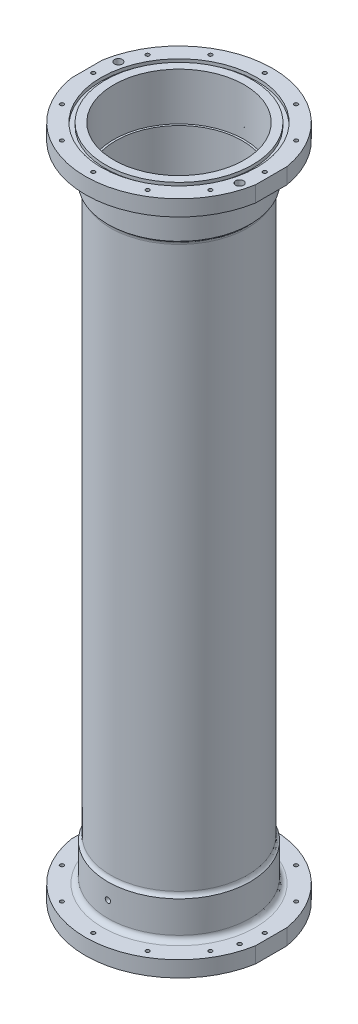
SolidWorks part; units mm, degrees
material "6061-T6 (SS)"
ref_plane "Front Plane" through (0, 0, 0) normal (0, 0, 1) x (1, 0, 0)
ref_plane "Top Plane" through (0, 0, 0) normal (0, 1, 0) x (1, 0, 0)
ref_plane "Right Plane" through (0, 0, 0) normal (1, 0, 0) x (0, 0, -1)
sketch "Sketch2" plane through (0, 0, 0) normal (0, 1, 0) x (1, 0, 0)
  circle A0 centre (0, 0) radius 38.1
  circle A1 centre (0, 0) radius 41.275
  dimension "D1" = 82.55
  dimension "D2" = 76.2
extrude "Base Cylinder" add sketch "Sketch2" along normal blind 406.4
sketch "Sketch3" plane through (0, 0, 0) normal (0, -1, 0) x (1, 0, 0)
  circle A0 centre (0, 0) radius 38.1
  circle A1 centre (0, 0) radius 56.3562
  dimension "D1" = 112.7125
extrude "Aft Flange" add sketch "Sketch3" against normal blind 9.525
sketch "Sketch34" plane through (0, 0, 0) normal (0, -1, 0) x (1, 0, 0)
  circle A0 centre (0, 0) radius 39.2906
  dimension "D1" = 78.5812
extrude "TemperatureInsert" cut sketch "Sketch34" against normal blind 28.575
sketch "Sketch6" plane through (0, 0, 0) normal (0, -1, 0) x (1, 0, 0)
  circle A0 centre (0, 0) radius 46.9011
  circle A1 centre (0, 0) radius 44.2849
  dimension "D1" = 93.8022
  dimension "D2" = 88.5698
extrude "Aft O-Ring" cut sketch "Sketch6" against normal blind 1.9812
sketch "Sketch33" plane through (0, 9.525, 0) normal (0, 1, 0) x (1, 0, 0)
  circle A0 centre (0, 0) radius 41.275
  circle A1 centre (0, 0) radius 42.8625
  dimension "D1" = 82.55
  dimension "D2" = 85.725
extrude "CriticalBoss" add sketch "Sketch33" along normal blind 22.225
sketch "Sketch For Bolt Holes" plane through (0, 0, 0) normal (0, -1, 0) x (1, 0, 0)
  circle A0 centre (-51.6255, 0) radius 1.5875
  circle A1 centre (-44.709, 25.8128) radius 1.5875
  circle A2 centre (-25.8128, 44.709) radius 1.5875
  circle A3 centre (0, 51.6255) radius 1.5875
  circle A4 centre (25.8127, 44.709) radius 1.5875
  circle A5 centre (44.709, 25.8128) radius 1.5875
  circle A6 centre (51.6255, 0) radius 1.5875
  circle A7 centre (44.709, -25.8127) radius 1.5875
  circle A8 centre (25.8128, -44.709) radius 1.5875
  circle A9 centre (0, -51.6255) radius 1.5875
  circle A10 centre (-25.8127, -44.709) radius 1.5875
  circle A11 centre (-44.709, -25.8128) radius 1.5875
  point P36 (0, 0)
  dimension "D2" = 3.175
  dimension "D1" = 51.6255
  dimension "D3" = 12
hole_wizard "Bolt Circle" positions "Sketch8" profile "Sketch9" hole size "#4-40" standard "ANSI Inch"
sketch "Sketch8" plane through (0, 0, 0) normal (0, -1, 0) x (-1, 0, 0)
  point P0 (-25.8127, -44.709)
  point P3 (-44.709, -25.8128)
  point P6 (-51.6255, 0)
  point P9 (-44.709, 25.8127)
  point P12 (-25.8128, 44.709)
  point P15 (0, 51.6255)
  point P18 (25.8127, 44.709)
  point P21 (44.709, 25.8128)
  point P24 (51.6255, 0)
  point P27 (44.709, -25.8128)
  point P30 (25.8128, -44.709)
  point P33 (0, -51.6255)
  point P36 (-25.8127, -44.709)
  point P38 (-44.709, -25.8128)
  point P40 (-51.6255, 0)
sketch "Sketch9" plane through (25.8127, 0, 44.709) normal (1, 0, 0) x (0, 0, -1)
  line L0 (0, 0) -> (0, 26.0792)
  line L1 (0, 26.0792) -> (1.1303, 25.4)
  line L2 (1.1303, 25.4) -> (1.1303, 0)
  line L5 (1.1303, 0) -> (0, 0)
  line L10 (0, 26.0792) -> (-1.1303, 25.4) construction
  line L11 (0, -6.35) -> (0, 107.95) construction
  dimension "Hole Dia." = 2.2606
  dimension "Hole Depth" = 25.4
  dimension "Drill Angle" = 118
fillet "CriticalBoss Flange" radius 3.175 2 edges at (0, 31.75, 41.275) (0, 9.525, -42.8625)
sketch "Dowel Hole Sketch" plane through (0, 0, 0) normal (0, -1, 0) x (1, 0, 0)
  line L0 (0, 0) -> (-51.6255, 0) construction
  line L1 (0, 0) -> (-49.8664, -13.3617) construction
  line L2 (0, 0) -> (0, -51.6255) construction
  line L3 (0, 0) -> (49.8664, 13.3617) construction
  circle A0 centre (0, 0) radius 51.6255
  circle A1 centre (-49.8664, -13.3617) radius 4.6172
  circle A2 centre (49.8664, 13.3617) radius 3.4532
  dimension "D1" = 15
hole_wizard "3/16 (0.1875) Press Dowel Hole1" positions "Sketch14" profile "Sketch12" hole size "3/16" standard "ANSI Inch"
sketch "Sketch14" plane through (0, 0, 0) normal (0, -1, 0) x (-1, 0, 0)
  point P0 (49.8664, 13.3617)
  point P3 (-49.8664, -13.3617)
sketch "Sketch12" plane through (-49.8664, 0, -13.3617) normal (1, 0, 0) x (0, 0, -1)
  line L0 (0, 0) -> (0, 7.7808)
  line L1 (0, 7.7808) -> (2.3812, 6.35)
  line L2 (2.3812, 6.35) -> (2.3812, 0)
  line L5 (2.3812, 0) -> (0, 0)
  line L10 (0, 7.7808) -> (-2.3813, 6.35) construction
  line L11 (0, -6.35) -> (0, 107.95) construction
  dimension "Hole Dia." = 4.7625
  dimension "Hole Depth" = 6.35
  dimension "Drill Angle" = 118
hole_wizard "3/32 (0.09375) Diameter Hole1" positions "Sketch19" profile "Sketch21" hole size "3/32" standard "ANSI Inch" end condition up to next
sketch "Sketch19" plane through (0, 0, 0) normal (0, -1, 0) x (-1, 0, 0)
  point P0 (-49.8664, -13.3617)
  point P3 (49.8664, 13.3617)
sketch "Sketch21" plane through (49.8664, 0, 13.3617) normal (1, 0, 0) x (0, 0, -1)
  line L0 (0, 0) -> (0, 398.6192)
  line L1 (0, 398.6192) -> (1.1906, 398.6192)
  line L2 (1.1906, 398.6192) -> (1.1906, 0)
  line L5 (1.1906, 0) -> (0, 0)
  line L11 (0, -6.35) -> (0, 107.95) construction
  dimension "Thru Hole Dia." = 2.3812
  dimension "Thru Hole Depth" = 398.6192
ref_plane "Hoop Mid-Plane" through (0, 203.2, 0) normal (0, 1, 0) x (1, 0, 0)
mirror "Forward Mirror BC and Pin" about plane through (0, 203.2, 0) normal (0, 1, 0) of "CriticalBoss Flange", "TemperatureInsert", "CriticalBoss", "Aft O-Ring", "3/16 (0.1875) Press Dowel Hole1", "3/32 (0.09375) Diameter Hole1", "Bolt Circle", "Aft Flange"
ref_plane "PressureTapHolePlane" [suppressed] through (0, 0, 42.8625) normal (0, 0, 1) x (1, 0, 0)
ref_plane "PressureTapHole2Plane" [suppressed] through (0, 0, -42.8625) normal (0, 0, 1) x (1, 0, 0)
sketch "Sketch35" plane through (0, 0, 42.8625) normal (0, 0, 1) x (1, 0, 0)
  line L0 (-56.3562, 0) -> (56.3562, 0) construction
  circle A0 centre (0, 22.225) radius 1.5875
  dimension "D1" = 22.225
  dimension "D2" = 3.175
extrude "Pressure Tap Aft Big" cut sketch "Sketch35" against normal blind 3.175
sketch "Sketch41" plane through (0, 0, 39.6875) normal (0, 0, 1) x (1, 0, 0)
  circle A0 centre (0, 22.225) radius 0.1984
extrude "Pressure Tap Aft Small" cut sketch "Sketch41" against normal up to next
sketch "Sketch42" plane through (0, 0, -42.8625) normal (0, 0, 1) x (1, 0, 0)
  line L0 (56.3562, 406.4) -> (-56.3562, 406.4) construction
  circle A0 centre (0, 384.175) radius 1.5875
  dimension "D1" = 22.225
  dimension "D2" = 3.175
extrude "Pressure Tap Foreward Big" cut sketch "Sketch42" along normal blind 3.175
sketch "Sketch43" plane through (0, 0, -39.6875) normal (0, 0, -1) x (-1, 0, 0)
  circle A0 centre (0, 384.175) radius 0.1984
  dimension "D1" = 0.3969
extrude "Pressure Tap Foreward Small" cut sketch "Sketch43" against normal up to next
sketch "Sketch44" plane through (0, 406.4, 0) normal (0, 1, 0) x (1, 0, 0)
  line L0 (0, -45.4025) -> (0, 45.4025) construction
  line L1 (55.5625, 11.3005) -> (57.15, 11.3005)
  line L2 (55.5625, 11.3005) -> (55.5625, -11.3005)
  line L3 (55.5625, -11.3005) -> (57.15, -11.3005)
  line L4 (57.15, 11.3005) -> (57.15, -11.3005)
  line L5 (55.5625, 11.3005) -> (57.15, -11.3005) construction
  line L6 (55.5625, -11.3005) -> (57.15, 11.3005) construction
  line L7 (-55.5625, -11.3005) -> (-57.15, -11.3005)
  line L8 (-57.15, 11.3005) -> (-57.15, -11.3005)
  line L9 (-55.5625, 11.3005) -> (-57.15, 11.3005)
  line L10 (-55.5625, 11.3005) -> (-55.5625, -11.3005)
  circle A0 centre (0, 0) radius 56.3562 construction
  point P0 (56.3562, 0)
  dimension "D1" = 1.5875
extrude "Mill Grips" cut sketch "Sketch44" against normal through all
